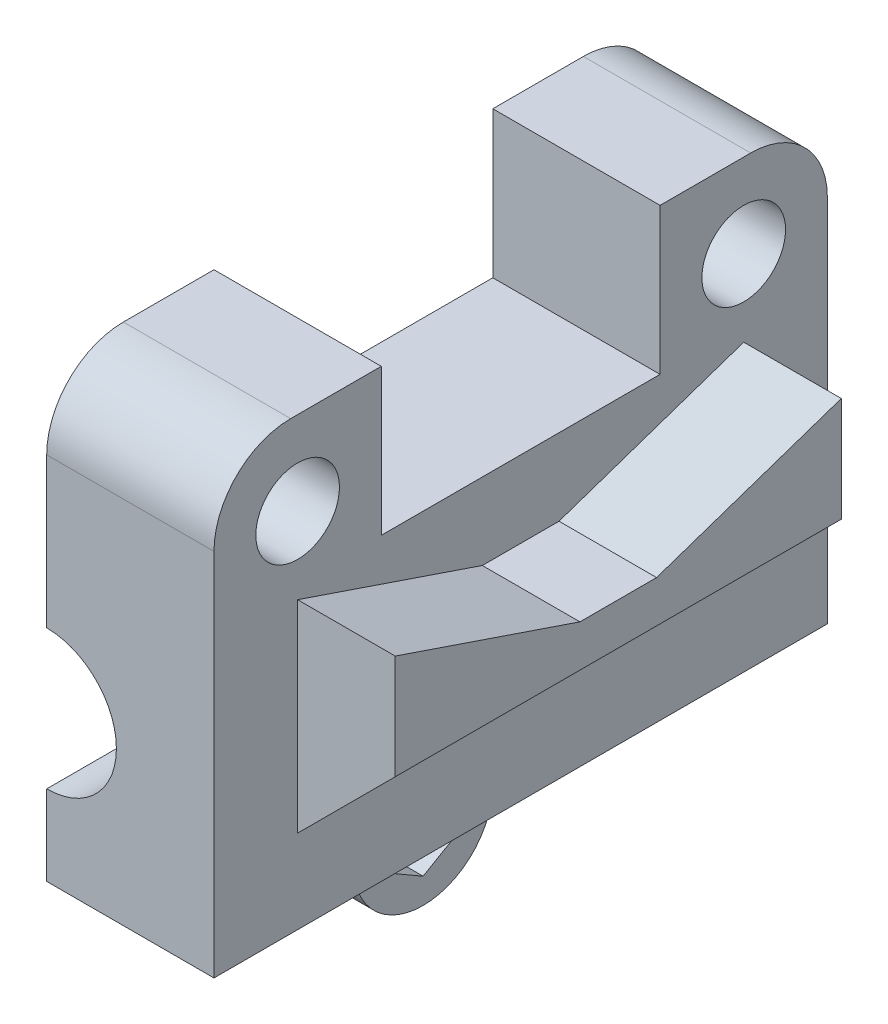
SolidWorks part; units mm, degrees
ref_plane "Front Plane" through (0, 0, 0) normal (0, 0, 1) x (1, 0, 0)
ref_plane "Top Plane" through (0, 0, 0) normal (0, 1, 0) x (1, 0, 0)
ref_plane "Right Plane" through (0, 0, 0) normal (1, 0, 0) x (0, 0, -1)
sketch "Sketch1" plane through (0, 0, 0) normal (1, 0, 0) x (0, 0, -1)
  line L1 (-22, -16) -> (22, -16)
  line L2 (-22, -16) -> (-22, 16)
  line L3 (-22, 16) -> (22, 16)
  line L4 (22, -16) -> (22, 16)
  line L5 (-22, -16) -> (22, 16) construction
  line L6 (-22, 16) -> (22, -16) construction
  point P0 (0, 0)
  dimension "D1" = 44
  dimension "D2" = 32
extrude "Boss-Extrude1" add sketch "Sketch1" along normal blind 12
sketch "Sketch2" plane through (0, 0, 0) normal (1, 0, 0) x (0, 0, -1)
  line L0 (-22, -16) -> (22, -16) construction
  line L1 (12.25, -13) -> (-12.25, -13)
  line L2 (12.25, -13) -> (12.25, 2.5)
  line L3 (12.25, 2.5) -> (-12.25, 2.5)
  line L4 (-12.25, -13) -> (-12.25, 2.5)
  line L5 (12.25, -13) -> (-12.25, 2.5) construction
  line L6 (12.25, 2.5) -> (-12.25, -13) construction
  point P0 (0, -5.25)
  dimension "D1" = 24.5
  dimension "D2" = 15.5
  dimension "D3" = 0
  dimension "D4" = 3
extrude "Cut-Extrude1" cut sketch "Sketch2" along normal blind 7.75 contours L2 L1 L4 L3
fillet "Fillet1" radius 7.75 2 edges at (7.75, 2.5, 0) (7.75, -13, 0)
sketch "Sketch3" plane through (0, 0, -12.25) normal (0, 0, 1) x (1, 0, 0)
  arc A0 (0, -13) -> (7.75, -5.25) centre (0, -5.25) ccw construction
  arc A1 (0, -13) -> (7.75, -5.25) centre (0, -5.25) ccw
  circle A2 centre (0, -5.25) radius 5
  line M3 (0, 2.5) -> (0, -13)
  dimension "D1" = 10
extrude "Cut-Extrude2" cut sketch "Sketch3" against normal through all both and the other way through all contours A2 M3 | A2 M3 region at (2.1221, -5.25, -12.25) region at (-2.1221, -5.25, -12.25)
sketch "Sketch4" plane through (12, 0, 0) normal (1, 0, 0) x (0, 0, -1)
  line L0 (22, 16) -> (-22, 16) construction
  line L2 (-10, 16) -> (10, 16)
  line L3 (-10, 16) -> (-10, 5.5)
  line L4 (-10, 5.5) -> (10, 5.5)
  line L5 (10, 16) -> (10, 5.5)
  circle A0 centre (-16, 10) radius 3
  circle A1 centre (16, 10) radius 3
  dimension "D1" = 6
  dimension "D2" = 6
  dimension "D3" = 6
  dimension "D4" = 6
  dimension "D5" = 6
  dimension "D6" = 6
  dimension "D7" = 32
  dimension "D8" = 10
  dimension "D9" = 10.5
extrude "Cut-Extrude3" cut sketch "Sketch4" against normal through all
sketch "Sketch5" plane through (12, 0, 0) normal (1, 0, 0) x (0, 0, -1)
  line L0 (-16, 10) -> (-16, 4.5)
  line L1 (-2.75, -3) -> (2.75, -3)
  line L2 (-2.75, -3) -> (-2.75, 0)
  line L3 (-2.75, 0) -> (2.75, 0)
  line L4 (2.75, -3) -> (2.75, 0)
  line L5 (-2.75, -3) -> (2.75, 0) construction
  line L6 (-2.75, 0) -> (2.75, -3) construction
  line L7 (16, 10) -> (16, 4.5)
  line L8 (-2.75, 0) -> (-16, 4.5)
  line L9 (2.75, 0) -> (16, 4.5)
  line L10 (2.75, -3) -> (16, 4.5)
  line L11 (-2.75, -3) -> (-16, 4.5)
  line L12 (16, 4.5) -> (16, -3)
  line L13 (16, -3) -> (2.75, -3)
  line L14 (-2.75, -3) -> (-16, -3)
  line L15 (-16, -3) -> (-16, 4.5)
  circle A0 centre (16, 10) radius 3 construction
  circle A1 centre (16, 10) radius 3
  circle A2 centre (-16, 10) radius 3 construction
  circle A3 centre (-16, 10) radius 3
  point P0 (0, -1.5)
  dimension "D1" = 10
  dimension "D2" = 3
  dimension "D3" = 5.5
  dimension "D4" = 0
  dimension "D5" = 5.5
  dimension "D6" = 5.5
extrude "Boss-Extrude4" add sketch "Sketch5" along normal blind 7 contours L15 L14 L11 | L11 L2 L8 | L1 L4 L3 L2 | L4 L10 L9 | L13 L12 L10 region at (12, 0.5, 7.1667) region at (12, -0.5, 11.5833) region at (12, -1.5, 0) region at (12, 0.5, -7.1667) region at (12, -0.5, -11.5833)
chamfer "Chamfer1" distance 7 angle 45 1 edges at (12, -3, 0)
sketch "Sketch6" plane through (12, 0, 0) normal (1, 0, 0) x (0, 0, -1)
  line L0 (16, -3) -> (-16, -3) construction
  line L1 (16, -3) -> (-16, -3)
  line L2 (16, -10) -> (-16, -10) construction
  line L3 (-13, -3) -> (13, -3)
  line L4 (-13, -3) -> (-13, -10)
  line L5 (-13, -10) -> (13, -10)
  line L6 (13, -3) -> (13, -10)
  line L7 (-16, -10) -> (-16, -3) construction
  line L8 (10, 5.5) -> (-10, 5.5)
  line L9 (-10, 5.5) -> (-10, 16)
  line L10 (-10, 16) -> (-22, 16)
  line L11 (-22, 16) -> (-22, -16)
  line L12 (-22, -16) -> (22, -16)
  line L13 (22, -16) -> (22, 16)
  line L14 (22, 16) -> (10, 16)
  line L15 (10, 16) -> (10, 5.5)
  line L16 (10, 5.5) -> (-10, 5.5)
  line L17 (-10, 5.5) -> (-10, 16)
  line L18 (-10, 16) -> (-22, 16)
  line L19 (-22, 16) -> (-22, -16)
  line L20 (-22, -16) -> (22, -16)
  line L21 (22, -16) -> (22, 16)
  line L22 (22, 16) -> (10, 16)
  line L23 (10, 16) -> (10, 5.5)
  line L24 (16, 4.5) -> (16, -10) construction
  line L25 (-2.75, 0) -> (2.75, 0) construction
  line L26 (-1.5, -3) -> (1.5, -3)
  line L27 (-1.5, -3) -> (-1.5, -10)
  line L28 (-1.5, -10) -> (1.5, -10)
  line L29 (1.5, -3) -> (1.5, -10)
  point P26 (0, 0)
  line M13 (16, -10) -> (-16, -10)
  dimension "D2" = 3
  dimension "D3" = 3
  dimension "D4" = 3
  dimension "D5" = 1.5
  dimension "D1" = 0
extrude "Cut-Extrude5" cut sketch "Sketch6" along normal through all contours L27 L1 L4 L5 | L1 L29 L6 M13 region at (12, -6.5, -7.25) region at (12, -6.5, 7.25)
fillet "Fillet4" radius 5.5 2 edges at (6, 16, -22) (6, 16, 22)
sketch "Sketch7" plane through (0, 0, 0) normal (1, 0, 0) x (0, 0, -1)
  line L0 (-22, -16) -> (22, -16) construction
  line L1 (5, -16) -> (-5, -16)
  line L2 (5, -16) -> (5, -26)
  line L3 (5, -26) -> (-5, -26)
  line L4 (-5, -16) -> (-5, -26)
  circle A0 centre (0, -21) radius 2
  dimension "D4" = 4
  dimension "D1" = 10
  dimension "D2" = 10
  dimension "D3" = 5
  dimension "D5" = 5
extrude "Boss-Extrude5" add sketch "Sketch7" along normal blind 5
sketch "Sketch8" plane through (5, 0, 0) normal (1, 0, 0) x (0, 0, -1)
  line L1 (0, -24.1754) -> (2.75, -22.5877)
  line L2 (2.75, -22.5877) -> (2.75, -19.4123)
  line L3 (2.75, -19.4123) -> (0, -17.8246)
  line L4 (0, -17.8246) -> (-2.75, -19.4123)
  line L5 (-2.75, -19.4123) -> (-2.75, -22.5877)
  line L6 (-2.75, -22.5877) -> (0, -24.1754)
  circle A0 centre (0, -21) radius 2 construction
  circle A1 centre (0, -21) radius 2
  circle A2 centre (0, -21) radius 2.75 construction
  dimension "D1" = 5.5
extrude "Cut-Extrude6" cut sketch "Sketch8" against normal blind 2
fillet "Fillet5" radius 5 2 edges at (2.5, -26, -5) (2.5, -26, 5)
